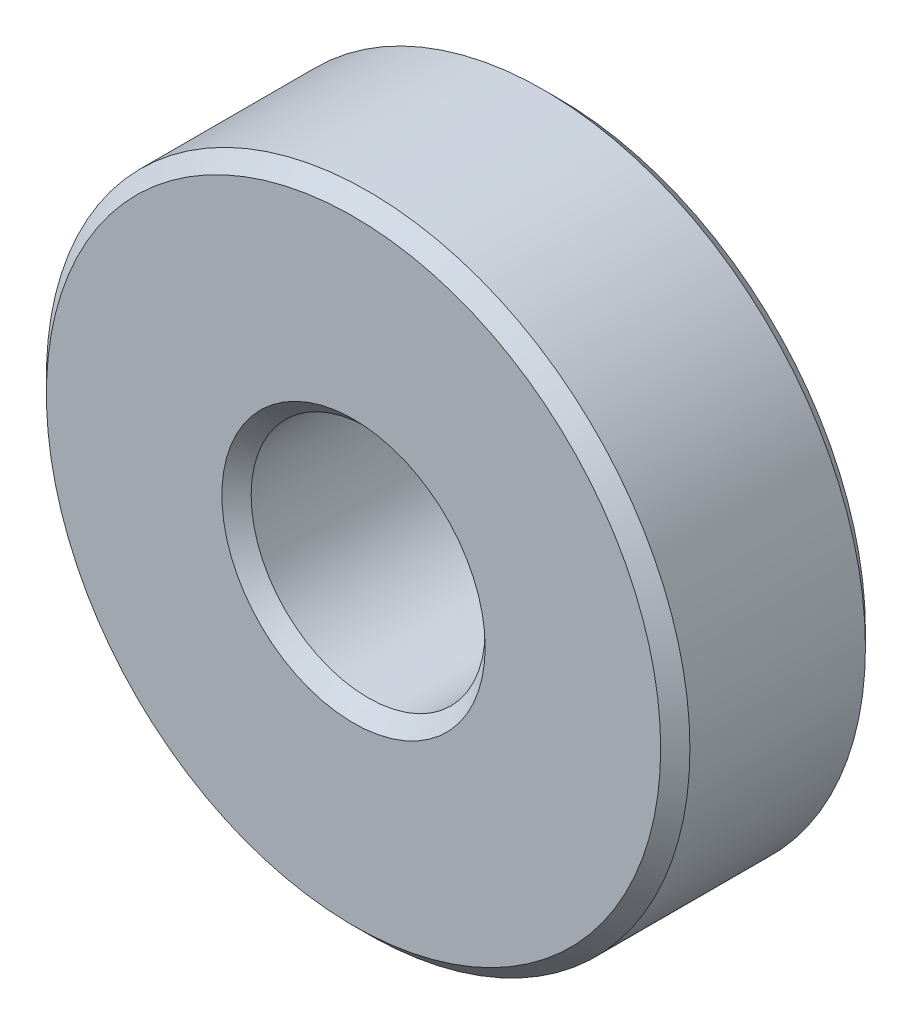
SolidWorks part; units mm, degrees
ref_plane "Płaszczyzna przednia" through (0, 0, 0) normal (0, 0, 1) x (1, 0, 0)
ref_plane "Płaszczyzna górna" through (0, 0, 0) normal (0, 1, 0) x (1, 0, 0)
ref_plane "Płaszczyzna prawa" through (0, 0, 0) normal (1, 0, 0) x (0, 0, -1)
sketch "Szkic1" plane through (0, 0, 0) normal (0, 0, 1) x (1, 0, 0)
  circle A0 centre (0, 0) radius 4
  circle A1 centre (0, 0) radius 11
  dimension "D1" = 8
  dimension "D2" = 22
extrude "Dodanie-wyciągnięcie1" add sketch "Szkic1" along normal blind 7
chamfer "Sfazowanie1" distance 0.5 angle 45 3 edges at (11, 0, 0) (4, 0, 7) (11, 0, 7)
